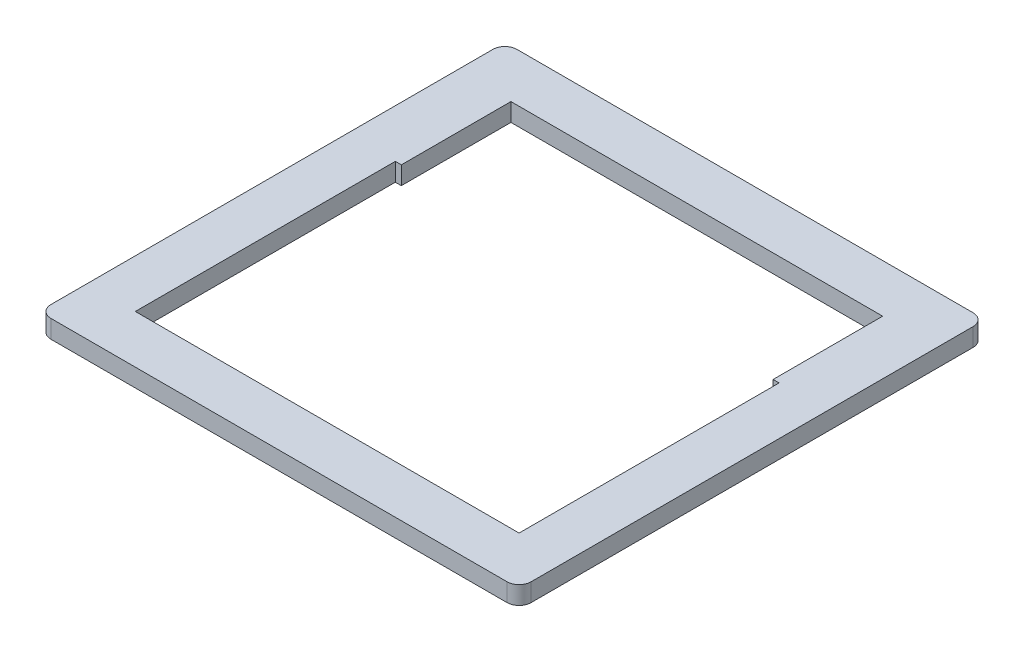
SolidWorks part; units mm, degrees
material "有机玻璃 (TM) GS 丙烯酸铸钣"
ref_plane "前视基准面" through (0, 0, 0) normal (0, 0, 1) x (1, 0, 0)
ref_plane "上视基准面" through (0, 0, 0) normal (0, 1, 0) x (1, 0, 0)
ref_plane "右视基准面" through (0, 0, 0) normal (1, 0, 0) x (0, 0, -1)
sketch "草图1" plane through (0, 0, 0) normal (0, 1, 0) x (1, 0, 0)
  line L0 (-28.1223, 20.6558) -> (-28.1223, 38.8446)
  line L1 (-29.1223, 20.6558) -> (-28.1223, 20.6558)
  line L2 (-29.1223, 20.6558) -> (-29.1223, -22.5027)
  line L3 (-29.1223, -22.5027) -> (34.5798, -22.5027)
  line L4 (34.5798, 20.6558) -> (34.5798, -22.5027)
  line L5 (-35.1223, 46.8446) -> (40.5798, 46.8446)
  line L6 (-37.1223, 44.8446) -> (-37.1223, -28.5027)
  line L7 (-35.1223, -30.5027) -> (40.5798, -30.5027)
  line L8 (42.5798, 44.8446) -> (42.5798, -28.5027)
  line L9 (33.5798, 20.6558) -> (33.5798, 38.8446)
  line L10 (-28.1223, 38.8446) -> (33.5798, 38.8446)
  line L11 (33.5798, 20.6558) -> (34.5798, 20.6558)
  arc A0 (-37.1223, 44.8446) -> (-35.1223, 46.8446) centre (-35.1223, 44.8446) cw
  arc A1 (-37.1223, -28.5027) -> (-35.1223, -30.5027) centre (-35.1223, -28.5027) ccw
  arc A2 (40.5798, -30.5027) -> (42.5798, -28.5027) centre (40.5798, -28.5027) ccw
  arc A3 (42.5798, 44.8446) -> (40.5798, 46.8446) centre (40.5798, 44.8446) ccw
  point P28 (0, 0)
  dimension "D6" = 2
  dimension "D7" = 2
  dimension "D1" = 8
  dimension "D2" = 8
  dimension "D3" = 8
  dimension "D4" = 1
  dimension "D5" = 1
  dimension "D8" = 8
extrude "凸台-拉伸1" add sketch "草图1" along normal blind 3
